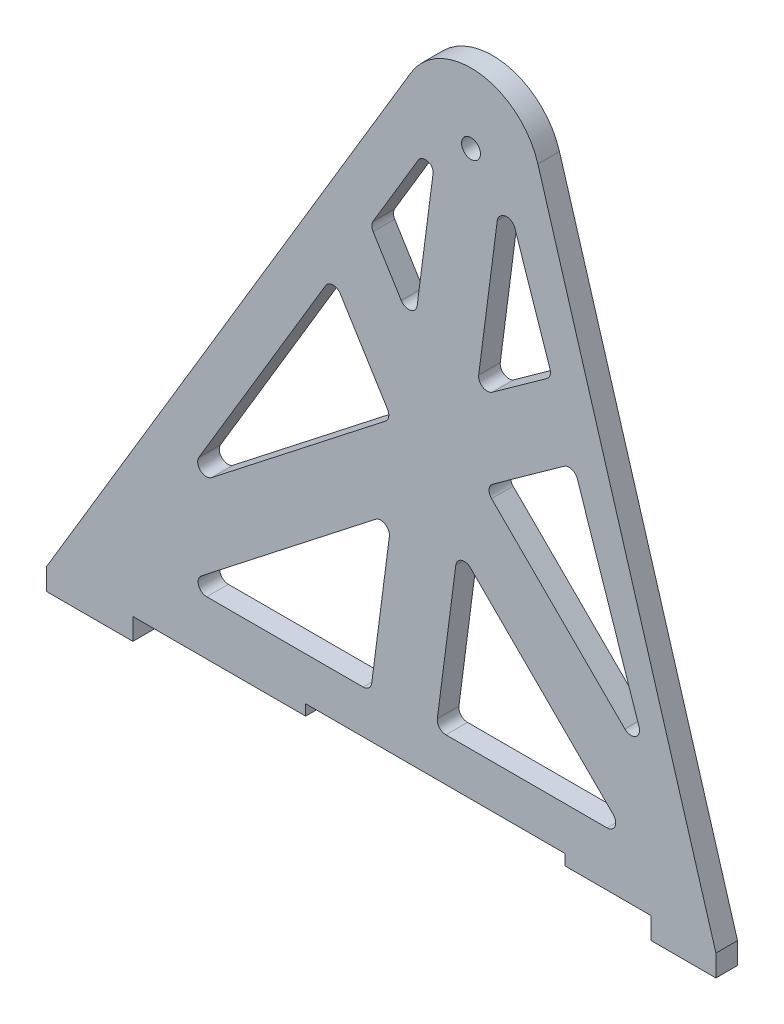
SolidWorks part; units mm, degrees
ref_plane "Front Plane" through (0, 0, 0) normal (0, 0, 1) x (1, 0, 0)
ref_plane "Top Plane" through (0, 0, 0) normal (0, 1, 0) x (1, 0, 0)
ref_plane "Right Plane" through (0, 0, 0) normal (1, 0, 0) x (0, 0, -1)
sketch "Sketch2" plane through (0, 0, 0) normal (0, 0, 1) x (1, 0, 0)
  line L0 (0, 2.5421) -> (203.2, 2.5421) construction
  line L1 (25.4, 2.5421) -> (76.2, 2.5421)
  line L2 (0, 2.5421) -> (107.2144, 181.9515)
  line L4 (76.2, 2.5421) -> (76.2, 5.7171)
  line L6 (0, 2.5421) -> (0, -3.8079)
  line L7 (0, -3.8079) -> (25.4, -3.8079)
  line L8 (25.4, 2.5421) -> (25.4, -3.8079)
  line L13 (76.2, 5.7171) -> (152.4, 5.7171)
  line L14 (152.4, 5.7171) -> (152.4, 2.5421)
  line L16 (152.4, 2.5421) -> (177.8, 2.5421)
  line L17 (0, -33.6061) -> (203.2, -33.6061) construction
  line L18 (177.8, 2.5421) -> (177.8, -3.8079)
  line L19 (177.8, -3.8079) -> (196.85, -3.8079)
  line L20 (196.85, -3.8079) -> (196.85, 2.5421)
  line L21 (196.85, 2.5421) -> (144.4949, 177.3126)
  arc A0 (144.4949, 177.3126) -> (107.2144, 181.9515) centre (124.8331, 171.4226) ccw
  circle A1 centre (124.8331, 171.4226) radius 11 construction
  circle A2 centre (124.8331, 171.4226) radius 4 construction
  circle A3 centre (124.8331, 171.4226) radius 2.7781
  point P21 (196.85, 13.5969)
  point P22 (181.6351, -2.3057)
  point P23 (152.9814, 2.5421)
  dimension "D3" = 22
  dimension "D4" = 9.525
  dimension "D5" = 8
  dimension "D6" = 5.5562
  dimension "D1" = 168.8805
  dimension "D2" = 124.8331
  dimension "D7" = 6.35
  dimension "D8" = 25.4
  dimension "D9" = 19.05
  dimension "D10" = 6.35
  dimension "D11" = 44.45
  dimension "D12" = 203.2
  dimension "D13" = 76.2
  dimension "D14" = 3.175
extrude "Boss-Extrude1" add sketch "Sketch2" along normal blind 6.35
sketch "Sketch4" plane through (0, 0, 6.35) normal (0, 0, 1) x (1, 0, 0)
  line L0 (111.2656, 163.9732) -> (10.9017, -3.9728)
  line L1 (136.5025, 161.2541) -> (185.679, 14.8218)
  line L2 (118.1161, 175.4367) -> (10.9017, -3.9728) construction
  line L3 (24.2818, 18.4171) -> (184.4716, 18.4171)
  line L4 (124.8331, 171.4226) -> (103.2992, 5.7171) construction
  line L5 (134.2787, 170.1951) -> (112.7448, 4.4896)
  line L6 (115.3875, 172.6501) -> (93.8537, 6.9445)
  line L7 (24.2818, 18.4171) -> (114.0662, 88.5698) construction
  line L8 (18.4173, 25.9226) -> (108.2017, 96.0754)
  line L9 (30.1462, 10.9115) -> (119.9306, 81.0643)
  line L10 (114.0662, 88.5698) -> (89.7368, 127.9475) construction
  line L11 (105.9631, 83.5633) -> (81.6336, 122.9409)
  line L12 (122.1693, 93.5763) -> (97.8399, 132.954)
  line L13 (0, 2.5421) -> (0, -3.8079)
  line L14 (0, -3.8079) -> (25.4, -3.8079)
  line L15 (25.4, -3.8079) -> (25.4, 2.5421)
  line L16 (25.4, 2.5421) -> (76.2, 2.5421)
  line L17 (76.2, 2.5421) -> (76.2, 5.7171)
  line L18 (76.2, 5.7171) -> (152.4, 5.7171)
  line L19 (152.4, 5.7171) -> (152.4, 2.5421)
  line L20 (152.4, 2.5421) -> (177.8, 2.5421)
  line L21 (177.8, -3.8079) -> (196.85, -3.8079)
  line L22 (177.8, 2.5421) -> (177.8, -3.8079)
  line L23 (152.4, 2.5421) -> (177.8, 2.5421)
  line L24 (196.85, -3.8079) -> (196.85, 2.5421)
  line L25 (107.2144, 181.9515) -> (0, 2.5421)
  line L26 (0, 2.5421) -> (0, -3.8079)
  line L27 (0, -3.8079) -> (25.4, -3.8079)
  line L28 (25.4, -3.8079) -> (25.4, 2.5421)
  line L29 (25.4, 2.5421) -> (76.2, 2.5421)
  line L30 (76.2, 2.5421) -> (76.2, 5.7171)
  line L31 (76.2, 5.7171) -> (152.4, 5.7171)
  line L32 (152.4, 5.7171) -> (152.4, 2.5421)
  line L34 (177.8, -3.8079) -> (196.85, -3.8079)
  line L35 (177.8, 2.5421) -> (177.8, -3.8079)
  line L38 (107.2144, 181.9515) -> (0, 2.5421)
  line L39 (114.0662, 88.5698) -> (151.8242, 115.631) construction
  line L40 (108.5175, 96.3118) -> (146.2755, 123.3729)
  line L41 (119.6148, 80.8279) -> (157.3728, 107.889)
  line L42 (114.0662, 88.5698) -> (184.4716, 18.4171) construction
  line L43 (120.7893, 95.3171) -> (191.1947, 25.1644)
  line L44 (107.3431, 81.8225) -> (177.7486, 11.6698)
  line L45 (97.8399, 132.954) -> (84.7663, 154.1138)
  line L46 (146.2755, 123.3729) -> (165.8724, 137.418)
  line L60 (196.85, -3.8079) -> (196.85, 2.5421)
  line L61 (196.85, 2.5421) -> (144.4949, 177.3126)
  line L62 (196.85, 2.5421) -> (144.4949, 177.3126)
  arc A0 (134.2787, 170.1951) -> (115.3875, 172.6501) centre (124.8331, 171.4226) ccw
  arc A1 (144.4949, 177.3126) -> (107.2144, 181.9515) centre (124.8331, 171.4226) ccw
  arc A2 (144.4949, 177.3126) -> (107.2144, 181.9515) centre (124.8331, 171.4226) ccw
  arc A3 (93.8537, 6.9445) -> (112.7448, 4.4896) centre (103.2992, 5.7171) ccw
  circle A4 centre (124.8331, 171.4226) radius 15.4781
  circle A5 centre (124.8331, 171.4226) radius 15.4781
  arc A6 (18.4173, 25.9226) -> (30.1462, 10.9115) centre (24.2818, 18.4171) ccw
  arc A7 (119.9306, 81.0643) -> (108.2017, 96.0754) centre (114.0662, 88.5698) ccw
  arc A8 (105.9631, 83.5633) -> (122.1693, 93.5763) centre (114.0662, 88.5698) ccw
  arc A9 (97.8399, 132.954) -> (81.6336, 122.9409) centre (89.7368, 127.9475) ccw
  arc A10 (108.5175, 96.3118) -> (119.6148, 80.8279) centre (114.0662, 88.5698) ccw
  arc A11 (157.3728, 107.889) -> (146.2755, 123.3729) centre (151.8242, 115.631) ccw
  arc A12 (120.7893, 95.3171) -> (107.3431, 81.8225) centre (114.0662, 88.5698) ccw
  arc A13 (177.7486, 11.6698) -> (191.1947, 25.1644) centre (184.4716, 18.4171) ccw
  point P18 (114.0662, 88.5698)
  point P31 (69.174, 53.4934)
  point P39 (101.9015, 108.2586)
  point P44 (132.9452, 102.1004)
  point P51 (149.2689, 53.4934)
  dimension "D6" = 9.525
  dimension "D5" = 12.7
  dimension "D1" = 0
  dimension "D2" = 12.7
  dimension "D3" = 12.7
extrude "Cut-Extrude1" cut sketch "Sketch4" against normal through all contours A5 L0 L45 L12 L6 | A5 L5 L40 L46 L1 | L41 L43 L1 | L44 L5 L3 | L9 L3 L6 | L8 L11 L0 region at (105.8659, 140.4246, 6.35) region at (136.4104, 133.3394, 6.35) region at (74.5143, 83.5502, 6.35) region at (153.8123, 77.3968, 6.35) region at (78.908, 34.5324, 6.35) region at (135.5183, 35.0086, 6.35)
fillet "Fillet1" radius 2.54 20 edges at (101.6272, 66.7629, 3.175) (95.3445, 18.4171, 3.175) (39.7522, 18.4171, 3.175) (154.9962, 106.1857, 3.175) (177.685, 38.6256, 3.175) (128.7558, 87.3792, 3.175) (113.8153, 160.5515, 3.175) (108.076, 116.3867, 3.175) (111.2656, 163.9732, 3.175) (84.2318, 118.7357, 3.175) (101.4783, 90.8221, 3.175) (37.8327, 41.0928, 3.175) (136.5025, 161.2541, 3.175) (148.6522, 125.0763, 3.175) (126.337, 109.083, 3.175) (132.7065, 158.0966, 3.175) (170.977, 18.4171, 3.175) (114.5547, 18.4171, 3.175) (121.0231, 68.1917, 3.175) (95.2417, 137.1592, 3.175)
